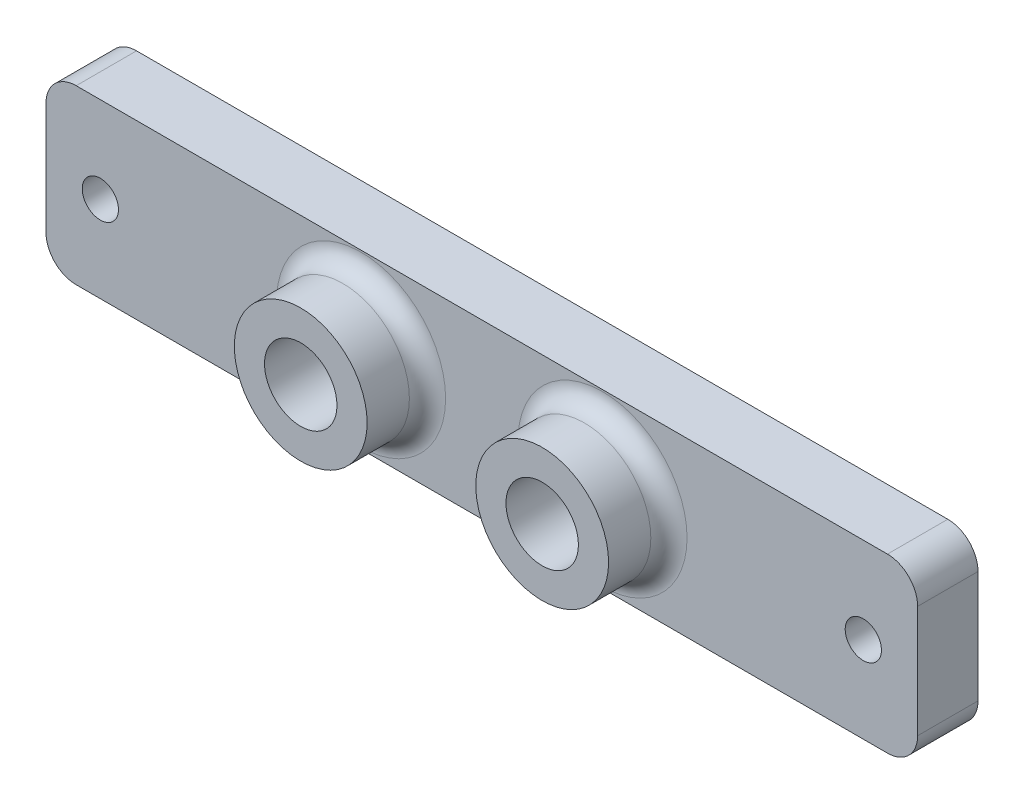
SolidWorks part; units mm, degrees
ref_plane "前视基准面" through (0, 0, 0) normal (0, 0, 1) x (1, 0, 0)
ref_plane "上视基准面" through (0, 0, 0) normal (0, 1, 0) x (1, 0, 0)
ref_plane "右视基准面" through (0, 0, 0) normal (1, 0, 0) x (0, 0, -1)
sketch "草图1" plane through (0, 0, 0) normal (0, 0, 1) x (1, 0, 0)
  line L2 (0, 0) -> (0, 3.14)
  line L6 (36.1, -7.14) -> (-36.1, -7.14)
  line L7 (36.1, -7.14) -> (36.1, 7.14)
  line L8 (36.1, 7.14) -> (-36.1, 7.14)
  line L9 (-36.1, -7.14) -> (-36.1, 7.14)
  circle A0 centre (31.6, 0) radius 1.5
  circle A1 centre (-31.6, 0) radius 1.5
  circle A2 centre (10, 0) radius 3
  circle A3 centre (-10, 0) radius 3
extrude "凸台-拉伸1" add sketch "草图1" along normal blind 5 contours L9 L6 L7 L8 A3 A2 A1 A0 region at (0, -6.404, 0)
fillet "圆角1" radius 2.5 4 edges at (36.1, -7.14, 2.5) (-36.1, -7.14, 2.5) (-36.1, 7.14, 2.5) (36.1, 7.14, 2.5)
sketch "草图2" plane through (0, 0, 5) normal (0, 0, 1) x (1, 0, 0)
  circle A0 centre (10, 0) radius 3 construction
  circle A1 centre (-10, 0) radius 3 construction
  circle A2 centre (10, 0) radius 3
  circle A3 centre (-10, 0) radius 3
  circle A4 centre (-10, 0) radius 5.5
  circle A5 centre (10, 0) radius 5.5
  dimension "D1" = 2.5
extrude "凸台-拉伸2" add sketch "草图2" along normal blind 5
fillet "圆角2" radius 1.5 2 edges at (15.5, 0, 5) (-4.5, 0, 5)
sketch "草图4" plane through (0, 0, 0) normal (0, 0, -1) x (-1, 0, 0)
  circle A0 centre (-4.5, 0.86) radius 2.5
  circle A1 centre (4.5, 0.86) radius 2.5
extrude "切除-拉伸1" cut sketch "草图4" against normal blind 2
